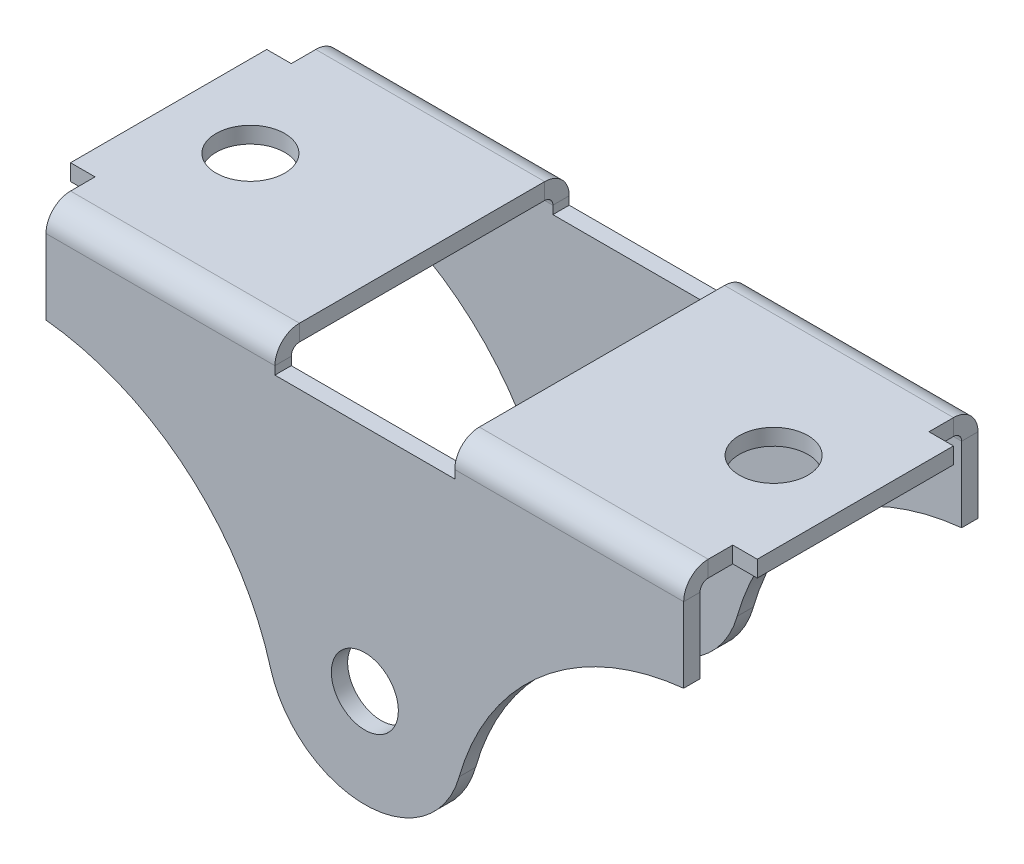
SolidWorks part; units mm, degrees
note: The reader was unsure of these and kept them because the rebuilt part matched: flange length of "Ребро-кромка1".
ref_plane "Спереди" through (0, 0, 0) normal (0, 0, 1) x (1, 0, 0)
ref_plane "Сверху" through (0, 0, 0) normal (0, 1, 0) x (1, 0, 0)
ref_plane "Справа" through (0, 0, 0) normal (1, 0, 0) x (0, 0, -1)
sketch "Эскиз1" plane through (0, 0, 0) normal (0, 0, 1) x (1, 0, 0)
  line L0 (-28.2857, 0) -> (0, 0) construction
  line L2 (-21, -5) -> (-21, 0)
  line L3 (0, -24.5714) -> (0, 4) construction
  line L4 (21, -5) -> (21, 0)
  line L5 (-21, 0) -> (21, 0)
  line L8 (0, 40.5714) -> (0, 4) construction
  line L13 (21, 0) -> (28.5, 0) construction
  arc A0 (-5.7726, -16.6361) -> (5.7726, -16.6361) centre (0, -15) ccw
  arc A1 (-5.7726, -16.6361) -> (-21, -5) centre (-21.1663, -20.9991) ccw
  arc A2 (5.7726, -16.6361) -> (21, -5) centre (21.1663, -20.9991) cw
  circle A3 centre (0, -15) radius 2.05
  point P5 (0, -15)
  point P18 (0, 0)
  point P20 (0, 16)
  point P34 (20, 8)
  point P35 (-20, 8)
  dimension "D3" = 6
  dimension "D5" = 4.1
  dimension "D6" = 16
  dimension "D2" = 5
  dimension "D4" = 21
base flange "Базовая кромка2" sketch "Эскиз1" thickness 1 reverse thickness direction no parameters "D1"=0.7366
edge flange "Ребро-кромка1" sketch "Эскиз7" flange angle 90 flange length 8 flange position material outside bend radius 0.5 thickness 1 parameters "D6"=10
sketch "Эскиз7" plane through (0, 0, -1) normal (0, 1, 0) x (1, 0, 0)
  line L0 (21, 0) -> (-21, 0) construction
  line L1 (21, 0) -> (-21, 0)
  line L2 (-21, 0) -> (-21, 8)
  line L3 (-21, 8) -> (21, 8)
  line L4 (21, 8) -> (21, 0)
bend "EdgeBend1" bend radius 0.5 bend angle 90 parameters "D5"=1
mirror "Зеркальное отражение1" about plane through (-21, 1, -9) normal (0, 0, 1) of bodies 107
bend "Зеркальное отражение сгиба1" bend radius 0.5 bend angle 90 parameters "D5"=2
sketch "Эскиз13" plane through (0, 0, 0) normal (0, 0, 1) x (1, 0, 0)
  line L0 (5.5, 1) -> (-5.5, 1)
  line L1 (21, 1) -> (-21, 1) construction
  line L2 (-5.5, 1) -> (-5.5, -1)
  line L3 (-5.5, -1) -> (5.5, -1)
  line L4 (0, 3.1575) -> (0, -7.0187) construction
  line L5 (5.5, 1) -> (5.5, -1)
  point P9 (0, -1)
  point P10 (0, 1)
  dimension "D1" = 2
  dimension "D2" = 11
extrude "Вырез-Вытянуть1" cut sketch "Эскиз13" against normal through all normal cut yes
sketch "Эскиз14" plane through (0, 1, 0) normal (0, 1, 0) x (1, 0, 0)
  line L0 (0, -1.4209) -> (0, 21.5947) construction
  line L1 (-24.4271, 9) -> (20.4911, 9) construction
  line L2 (-5.5, 16.5) -> (-5.5, 1.5) construction
  line L3 (-21, 18) -> (-19.5, 18)
  line L4 (-21, 18) -> (-21, 15)
  line L5 (-21, 15) -> (-19.5, 15)
  line L6 (-19.5, 18) -> (-19.5, 15)
  line L7 (-21, 3) -> (-19.5, 3)
  line L8 (-19.5, 0) -> (-19.5, 3)
  line L9 (-21, 0) -> (-19.5, 0)
  line L10 (-21, 0) -> (-21, 3)
  line L11 (21, 0) -> (21, 3)
  line L12 (21, 0) -> (19.5, 0)
  line L13 (19.5, 0) -> (19.5, 3)
  line L14 (21, 3) -> (19.5, 3)
  line L15 (21, 15) -> (19.5, 15)
  line L16 (19.5, 18) -> (19.5, 15)
  line L17 (21, 18) -> (19.5, 18)
  line L18 (21, 18) -> (21, 15)
  circle A0 centre (-16, 9) radius 2.1
  circle A1 centre (16, 9) radius 2.1
  dimension "D1" = 4.2
  dimension "D2" = 16
  dimension "D3" = 6
  dimension "D4" = 14
extrude "Вырез-Вытянуть2" cut sketch "Эскиз14" against normal through all normal cut yes
ref_plane "Плоскость1" through (0, 0, -9) normal (0, 0, -1) x (-1, 0, 0)
ref_plane "Плоскость2" through (0, 0, 0) normal (-1, 0, 0) x (0, 0, 1)
sketch "Сгиб-Линии1" plane through (0, 0, 0) normal (0, 1, 0) x (1, 0, 0)
sketch "Граничная рамка1" plane through (0, 0, 0) normal (0, 1, 0) x (1, 0, 0)
sheet metal parameters "Листовой металл6" thickness 1 parameters "D1"=0.7366
flat pattern "Развертка6" [suppressed]
sketch "Сгиб-Линии3" plane through (0, 0, 0) normal (0, 1, 0) x (1, 0, 0)
sketch "Граничная рамка3" [suppressed] plane through (0, 0, 0) normal (0, 1, 0) x (1, 0, 0)
sheet metal parameters "Листовой металл7" thickness 1 parameters "D1"=0.7366
flat pattern "Развертка6" [suppressed]
sketch "Сгиб-Линии3" plane through (0, 0, 0) normal (0, 1, 0) x (1, 0, 0)
sketch "Граничная рамка3" [suppressed] plane through (0, 0, 0) normal (0, 1, 0) x (1, 0, 0)
bend of the flat pattern "Плоское состояние-<EdgeBend1>1"
sheet metal parameters "Листовой металл9" thickness 1 parameters "D1"=0.7366
flat pattern "Развертка9" [suppressed]
sketch "Сгиб-Линии4" plane through (0, 0, 0) normal (0, 1, 0) x (1, 0, 0)
sketch "Граничная рамка4" [suppressed] plane through (0, 0, 0) normal (0, 1, 0) x (1, 0, 0)
bend of the flat pattern "Плоское состояние-<EdgeBend1>2"
bend of the flat pattern "Плоское состояние-<Зеркальное отражение сгиба1>1"
sheet metal parameters "Листовой металл10" thickness 1 parameters "D1"=0.7366
flat pattern "Развертка9" [suppressed]
sketch "Сгиб-Линии4" plane through (0, 0, 0) normal (0, 1, 0) x (1, 0, 0)
sketch "Граничная рамка4" [suppressed] plane through (0, 0, 0) normal (0, 1, 0) x (1, 0, 0)
bend of the flat pattern "Плоское состояние-<EdgeBend1>2"
bend of the flat pattern "Плоское состояние-<Зеркальное отражение сгиба1>1"
sheet metal parameters "Листовой металл11" thickness 1 parameters "D1"=0.7366
flat pattern "Развертка9" [suppressed]
sketch "Сгиб-Линии4" plane through (0, 0, 0) normal (0, 1, 0) x (1, 0, 0)
sketch "Граничная рамка4" [suppressed] plane through (0, 0, 0) normal (0, 1, 0) x (1, 0, 0)
bend of the flat pattern "Плоское состояние-<EdgeBend1>2"
bend of the flat pattern "Плоское состояние-<Зеркальное отражение сгиба1>1"
